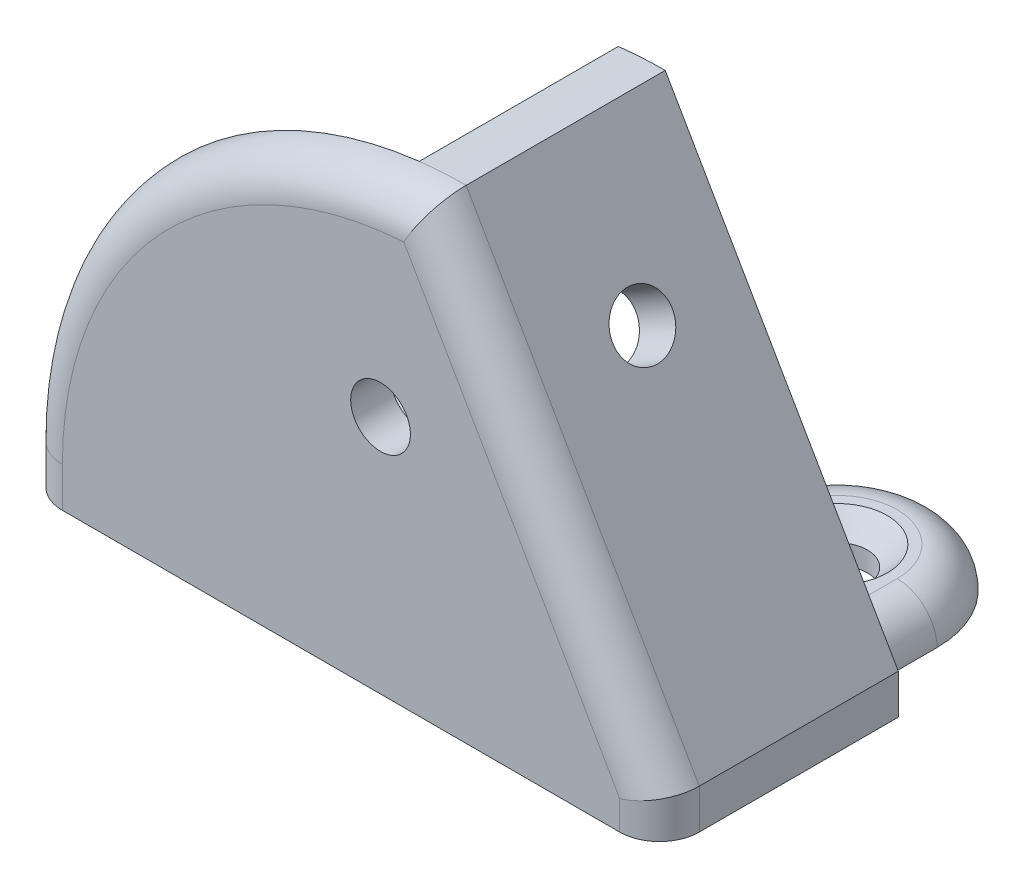
SolidWorks part; units mm, degrees
ref_plane "Front Plane" through (0, 0, 0) normal (0, 0, 1) x (1, 0, 0)
ref_plane "Top Plane" through (0, 0, 0) normal (0, 1, 0) x (1, 0, 0)
ref_plane "Right Plane" through (0, 0, 0) normal (1, 0, 0) x (0, 0, -1)
sketch "Sketch1" plane through (0, 0, 0) normal (0, 0, 1) x (1, 0, 0)
  line L0 (0, 0) -> (0, 4)
  line L1 (0, 0) -> (-64, 0)
  line L2 (-64, 0) -> (-64, 4)
  line L3 (0, 4) -> (-23.4256, 44.5744)
  arc A0 (-64, 4) -> (-23.4256, 44.5744) centre (-23.4256, 4) cw
  dimension "D1" = 60
  dimension "D2" = 4
  dimension "D3" = 64
extrude "Boss-Extrude1" add sketch "Sketch1" against normal blind 4
sketch "Sketch2" plane through (0, 0, -4) normal (0, 0, -1) x (-1, 0, 0)
  line L0 (64, 4) -> (35.4153, 4)
  line L1 (14.3709, 20.45) -> (28.1404, 44.2995)
  line L2 (0, 4) -> (23.4256, 44.5744) construction
  line L3 (64, 0) -> (0, 0) construction
  line L4 (14.3709, 20.45) -> (31.6914, 10.45)
  line L5 (31.6914, 10.45) -> (35.4153, 8.3) construction
  line L6 (23.4256, 44.5744) -> (27.0807, 42.4641) construction
  line L7 (0, 0) -> (5.604, -3.2355) construction
  line L11 (0, 0) -> (64, 0)
  line L12 (64, 0) -> (64, 4)
  line L13 (23.4256, 44.5744) -> (0, 4)
  line L14 (0, 4) -> (0, 0)
  line L15 (0, 0) -> (64, 0)
  line L16 (64, 0) -> (64, 4)
  line L17 (23.4256, 44.5744) -> (0, 4)
  line L18 (0, 4) -> (0, 0)
  arc A0 (64, 4) -> (23.4256, 44.5744) centre (23.4256, 4) ccw construction
  arc A1 (31.6914, 10.45) -> (35.4153, 4) centre (35.4153, 8.3) ccw
  arc A3 (64, 4) -> (23.4256, 44.5744) centre (23.4256, 4) ccw
  arc A4 (28.1404, 44.2995) -> (23.4256, 44.5744) centre (23.4256, 4) ccw
  point P15 (23.0311, 15.45)
  dimension "D4" = 4.3
  dimension "D1" = 24.8956
  dimension "D2" = 4
  dimension "D3" = 20
  dimension "D6" = 4.2205
  dimension "D5" = 0
extrude "Boss-Extrude2" add sketch "Sketch2" along normal blind 20
sketch "Sketch3" plane through (-12.4478, 21.5603, 0) normal (-0.5, 0.866, 0) x (0.866, 0.5, 0)
  line L2 (-22.2205, 24) -> (-2.2205, 24) construction
  line L3 (-22.2205, 24) -> (-22.2205, 4) construction
  circle A0 centre (-12.2205, 14) radius 3
  point P6 (-12.2205, 24)
  point P7 (-22.2205, 14)
  dimension "D1" = 6
extrude "Cut-Extrude1" cut sketch "Sketch3" against normal through all
ref_plane "Plane1" through (-10.4478, 18.0962, 0) normal (-0.5, 0.866, 0) x (-0.866, -0.5, 0)
sketch "Sketch4" plane through (-10.4478, 18.0962, 0) normal (-0.5, 0.866, 0) x (-0.866, -0.5, 0)
  circle A0 centre (12.2205, -14) radius 5
  dimension "D1" = 10
extrude "Cut-Extrude2" cut sketch "Sketch4" against normal through all
sketch "Sketch5" plane through (-1.923, -1.1103, 0) normal (-0.866, -0.5, 0) x (0, 0, 1)
  line L0 (-24, 24.8956) -> (-4, 24.8956) construction
  circle A0 centre (-14, 34.8957) radius 3
  point P4 (-14, 24.8956)
  point P5 (-14, 24.8956)
  dimension "D2" = 6
  dimension "D1" = 10
extrude "Cut-Extrude3" cut sketch "Sketch5" against normal through all
sketch "Sketch6" plane through (0, 4, 0) normal (0, 1, 0) x (1, 0, 0)
  line L0 (-64, 24) -> (-64, 4) construction
  circle A0 centre (-52, 14) radius 3
  point P4 (-64, 14)
  dimension "D2" = 6
  dimension "D1" = 12
extrude "Cut-Extrude4" cut sketch "Sketch6" against normal through all
sketch "Sketch7" plane through (0, 0, -4) normal (0, 0, -1) x (-1, 0, 0)
  line L0 (14.3709, 20.45) -> (28.1404, 44.2995) construction
  line L1 (31.6914, 10.45) -> (14.3709, 20.45) construction
  circle A0 centre (28.0311, 24.1103) radius 3
  dimension "D3" = 6
  dimension "D1" = 10
  dimension "D2" = 10
extrude "Cut-Extrude5" cut sketch "Sketch7" against normal through all
sketch "Sketch8" plane through (0, 0, 0) normal (0, 1, 0) x (1, 0, 0)
  line L0 (0, 24) -> (-64, 24) construction
  line L1 (-24.1111, 24) -> (-4.1111, 24)
  line L2 (-24.1111, 24) -> (-24.1111, 32)
  line L3 (-24.1111, 32) -> (-4.1111, 32) construction
  line L4 (-4.1111, 24) -> (-4.1111, 32)
  arc A0 (-24.1111, 32) -> (-4.1111, 32) centre (-14.1111, 32) cw
  dimension "D1" = 20
  dimension "D2" = 8
extrude "Boss-Extrude3" add sketch "Sketch8" along normal blind 4
ref_axis "Axis1" through (-14.1111, 4, -32) along (0, -1, 0)
ref_plane "Plane2" through (0, 0, -32) normal (0, 0, 1) x (1, 0, 0)
sketch "Sketch9" plane through (0, 0, -32) normal (0, 0, 1) x (1, 0, 0)
  line L0 (-17.1111, 0) -> (-17.1111, 2)
  line L1 (-24.1111, 0) -> (-4.1111, 0) construction
  line L2 (-17.1111, 2) -> (-19.1111, 4)
  line L3 (-4.1111, 4) -> (-24.1111, 4) construction
  line L4 (-14.1111, 4) -> (-14.1111, 0) construction
  line L5 (-19.1111, 4) -> (-14.1111, 4)
  line L6 (-14.1111, 4) -> (-14.1111, 0)
  line L7 (-14.1111, 0) -> (-17.1111, 0)
  dimension "D1" = 135
  dimension "D2" = 2
  dimension "D3" = 3
revolve "Cut-Revolve2" cut sketch "Sketch9" angle 360 about L6
fillet "Fillet1" radius 4 3 edges at (-24.1111, 4, -28) (-14.1111, 4, -42) (-4.1111, 4, -28)
fillet "Fillet2" radius 4 4 edges at (-64, 2, 0) (0, 2, 0) (-11.7128, 24.2872, 0) (-52.116, 32.6904, 0)
